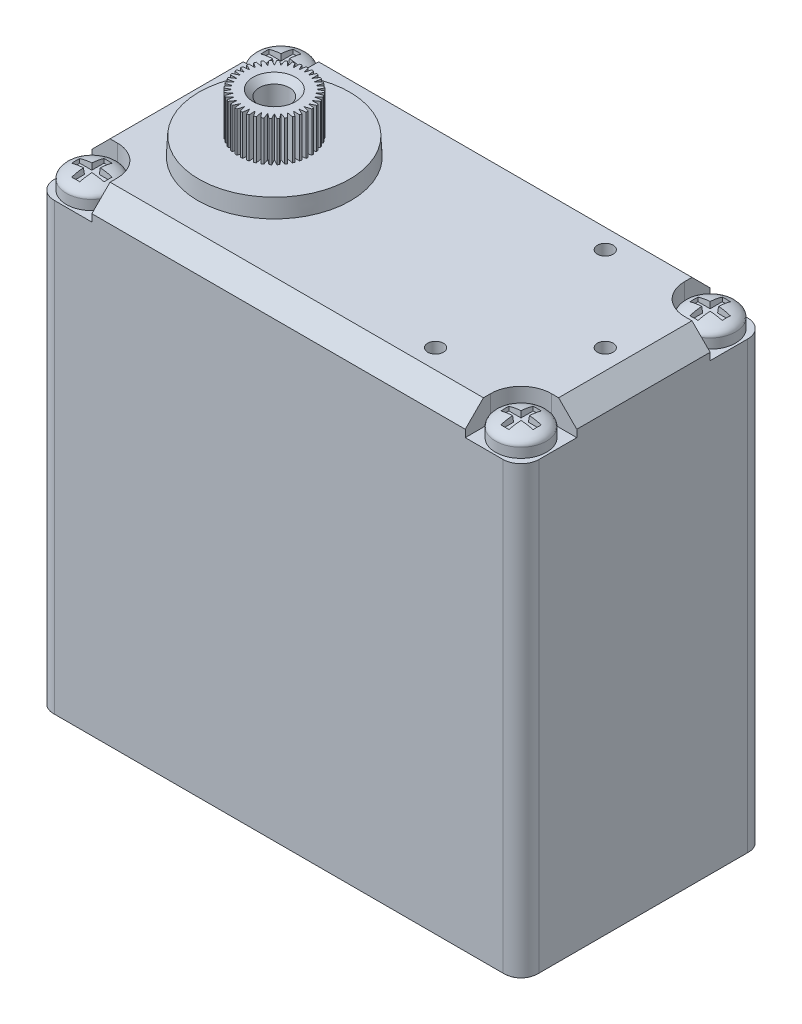
SolidWorks part; units mm, degrees
ref_plane "Front" through (0, 0, 0) normal (0, 0, 1) x (1, 0, 0)
ref_plane "Top" through (0, 0, 0) normal (0, 1, 0) x (1, 0, 0)
ref_plane "Right" through (0, 0, 0) normal (1, 0, 0) x (0, 0, -1)
sketch "Sketch1" plane through (0, 0, 0) normal (0, 0, 1) x (1, 0, 0)
  line L1 (20, 20.15) -> (-20, 20.15)
  line L2 (20, 20.15) -> (20, -20.15)
  line L3 (20, -20.15) -> (-20, -20.15)
  line L4 (-20, 20.15) -> (-20, -20.15)
  line L5 (20, 20.15) -> (-20, -20.15) construction
  line L6 (20, -20.15) -> (-20, 20.15) construction
  point P0 (0, 0)
  dimension "D1" = 40
  dimension "D2" = 40.3
extrude "Boss-Extrude1" add sketch "Sketch1" along normal mid plane 20.2
sketch "Sketch2" plane through (0, -20.15, 0) normal (0, -1, 0) x (1, 0, 0)
  line L1 (-20, 10.1) -> (-20, -10.1) construction
  circle A0 centre (-10.45, 0) radius 6.3
  dimension "D1" = 12.6
  dimension "D2" = 3.25
  dimension "D3" = 9.55
extrude "Boss-Extrude2" add sketch "Sketch2" along normal blind 1.5 draft 3
sketch "Sketch3" plane through (0, -20.15, 0) normal (0, -1, 0) x (1, 0, 0)
  circle A0 centre (-10.45, 0) radius 3
  dimension "D1" = 6
extrude "Boss-Extrude3" add sketch "Sketch3" along normal blind 5.4
sketch "Sketch9" plane through (0, -25.55, 0) normal (0, -1, 0) x (1, 0, 0)
  circle A0 centre (-10.45, 0) radius 1.2
  dimension "D1" = 2.4
extrude "Cut-Extrude4" cut sketch "Sketch9" against normal blind 5
sketch "Sketch4" plane through (0, 20.15, 0) normal (0, 1, 0) x (1, 0, 0)
  circle A1 centre (-10.45, 0) radius 6.3
  circle A2 centre (-10.45, 0) radius 6.3
  dimension "D1" = 0
extrude "Boss-Extrude4" add sketch "Sketch4" along normal blind 1.5 draft 3
sketch "Sketch5" plane through (0, 21.65, 0) normal (0, 1, 0) x (1, 0, 0)
  circle A0 centre (-10.45, 0) radius 2.95
  dimension "D1" = 5.9
extrude "Boss-Extrude5" add sketch "Sketch5" along normal blind 3.3 separate body
sketch "Sketch7" plane through (0, 24.95, 0) normal (0, 1, 0) x (1, 0, 0)
  circle A0 centre (-10.45, 0) radius 1.25
  dimension "D1" = 2.5
extrude "Cut-Extrude2" cut sketch "Sketch7" against normal blind 5
sketch "Sketch8" plane through (0, 24.95, 0) normal (0, 1, 0) x (1, 0, 0)
  line L0 (-8, 0) -> (-7.5, 0.15)
  line L1 (-8, 0) -> (-7.5, -0.15)
  line L2 (-7.5, -0.15) -> (-7.5, 0.15)
  circle A1 centre (-10.45, 0) radius 2.95 construction
  point P2 (-7.5, 0)
  dimension "D1" = 0.5
  dimension "D2" = 0.3
extrude "Cut-Extrude3" cut sketch "Sketch8" against normal through all
sketch "Sketch10" plane through (-20, 0, 0) normal (-1, 0, 0) x (0, 0, 1)
  line L0 (10.1, -20.15) -> (-10.1, -20.15) construction
  line L1 (3.5, -9.85) -> (-3.5, -9.85)
  line L2 (3.5, -9.85) -> (3.5, -13.35)
  line L3 (3.5, -13.35) -> (-3.5, -13.35)
  line L4 (-3.5, -9.85) -> (-3.5, -13.35)
  line L5 (3.5, -9.85) -> (-3.5, -13.35) construction
  line L6 (3.5, -13.35) -> (-3.5, -9.85) construction
  point P0 (0, -11.6)
  dimension "D1" = 7
  dimension "D2" = 3.5
  dimension "D3" = 6.8
extrude "Cut-Extrude5" cut sketch "Sketch10" against normal blind 4.9
sketch "Sketch11" plane through (-15.1, 0, 0) normal (-1, 0, 0) x (0, 0, 1)
  line L1 (-0.25, -12.55) -> (0.25, -12.55)
  line L2 (-0.25, -12.55) -> (-0.25, -12.05)
  line L3 (-0.25, -12.05) -> (0.25, -12.05)
  line L4 (0.25, -12.55) -> (0.25, -12.05)
  line L5 (-0.25, -12.55) -> (0.25, -12.05) construction
  line L6 (-0.25, -12.05) -> (0.25, -12.55) construction
  line L7 (3.5, -13.35) -> (-3.5, -13.35) construction
  line L9 (1.75, -12.55) -> (2.25, -12.55)
  line L10 (1.75, -12.55) -> (1.75, -12.05)
  line L11 (1.75, -12.05) -> (2.25, -12.05)
  line L12 (2.25, -12.55) -> (2.25, -12.05)
  line L13 (1.75, -12.55) -> (2.25, -12.05) construction
  line L14 (1.75, -12.05) -> (2.25, -12.55) construction
  line L15 (-2.25, -12.55) -> (-1.75, -12.55)
  line L16 (-2.25, -12.55) -> (-2.25, -12.05)
  line L17 (-2.25, -12.05) -> (-1.75, -12.05)
  line L18 (-1.75, -12.55) -> (-1.75, -12.05)
  line L19 (-2.25, -12.55) -> (-1.75, -12.05) construction
  line L20 (-2.25, -12.05) -> (-1.75, -12.55) construction
  point P0 (0, -12.3)
  point P5 (2, -12.3)
  point P13 (-2, -12.3)
  dimension "D1" = 0.5
  dimension "D2" = 0.8
  dimension "D3" = 1.5
  dimension "D4" = 1.5
extrude "Boss-Extrude6" add sketch "Sketch11" along normal blind 3.5 separate body
chamfer "Chamfer4" distance 0.1 angle 45 4 edges at (-18.6, -12.55, -2) (-18.6, -12.3, -2.25) (-18.6, -12.05, -2) (-18.6, -12.3, -1.75)
chamfer "Chamfer5" distance 0.1 angle 45 4 edges at (-18.6, -12.55, 0) (-18.6, -12.3, -0.25) (-18.6, -12.05, 0) (-18.6, -12.3, 0.25)
chamfer "Chamfer6" distance 0.1 angle 45 4 edges at (-18.6, -12.55, 2) (-18.6, -12.3, 1.75) (-18.6, -12.05, 2) (-18.6, -12.3, 2.25)
pattern_circular "CirPattern1" count 40 over 360 about axis through (-10.45, 24.95, 0) along (0, -1, 0) of "Cut-Extrude3" reverse direction yes
sketch "Sketch6" plane through (0, 20.15, 0) normal (0, 1, 0) x (1, 0, 0)
  line L0 (20, 10.1) -> (-20, 10.1) construction
  line L1 (-20, 10.1) -> (-15.4, 10.1)
  line L2 (-20, 10.1) -> (-20, 5.5)
  line L3 (-20, 5.5) -> (-17.9, 5.5)
  line L4 (-15.4, 10.1) -> (-15.4, 8)
  line L5 (-20, -10.1) -> (-20, 10.1) construction
  line L6 (0, -11.11) -> (0, 11.11) construction
  line L7 (15.4, 10.1) -> (15.4, 8)
  line L8 (20, 5.5) -> (17.9, 5.5)
  line L9 (20, 10.1) -> (20, 5.5)
  line L10 (20, 10.1) -> (15.4, 10.1)
  line L11 (-22, 0) -> (22, 0) construction
  line L12 (20, -10.1) -> (15.4, -10.1)
  line L13 (20, -10.1) -> (20, -5.5)
  line L14 (20, -5.5) -> (17.9, -5.5)
  line L15 (15.4, -10.1) -> (15.4, -8)
  line L16 (-15.4, -10.1) -> (-15.4, -8)
  line L17 (-20, -5.5) -> (-17.9, -5.5)
  line L18 (-20, -10.1) -> (-20, -5.5)
  line L19 (-20, -10.1) -> (-15.4, -10.1)
  arc A0 (-17.9, 5.5) -> (-15.4, 8) centre (-17.9, 8) ccw
  arc A1 (17.9, 5.5) -> (15.4, 8) centre (17.9, 8) cw
  arc A2 (17.9, -5.5) -> (15.4, -8) centre (17.9, -8) ccw
  arc A3 (-17.9, -5.5) -> (-15.4, -8) centre (-17.9, -8) cw
  dimension "D1" = 2.5
  dimension "D2" = 4.6
extrude "Cut-Extrude1" cut sketch "Sketch6" against normal blind 2.1
chamfer "Chamfer2" distance 1.5 angle 45 4 edges at (20, -20.15, 0) (0, -20.15, -10.1) (-20, -20.15, 0) (0, -20.15, 10.1)
fillet "Fillet1" radius 1.5 4 edges at (20, -0.3, -10.1) (20, -0.3, 10.1) (-20, -0.3, -10.1) (-20, -0.3, 10.1)
fillet "Fillet2" radius 2.1 4 edges at (-19.0303, -19.6197, 9.1303) (19.0303, -19.6197, 9.1303) (19.0303, -19.6197, -9.1303) (-19.0303, -19.6197, -9.1303)
chamfer "Chamfer1" distance 1.5 angle 45 4 edges at (20, 20.15, 0) (-20, 20.15, 0) (0, 20.15, -10.1) (0, 20.15, 10.1)
chamfer "Chamfer3" distance 0.5 angle 45 1 edges at (-11.7, 24.95, 0)
fillet "Fillet3" radius 0.5 1 edges at (-7.45, -25.55, 0)
sketch "Sketch12" plane through (0, 18.05, 0) normal (0, 1, 0) x (1, 0, 0)
  line L0 (-20, 10.1) -> (-15.4, 10.1) construction
  line L1 (-20, 10.1) -> (-20, 5.5) construction
  circle A0 centre (-17.7, 7.8) radius 2.1
  point P4 (-17.7, 10.1)
  point P7 (-20, 7.8)
  dimension "D1" = 4.2
extrude "Boss-Extrude7" add sketch "Sketch12" along normal blind 0.8 separate body
dome "Dome1" faces to dome 1 distance 0.8 reverse direction no elliptical dome yes face at (-19.8, 18.85, -7.8) parameters "D1"=0.8
sketch "Sketch13" plane through (0, 18.05, 0) normal (0, -1, 0) x (1, 0, 0)
  line L1 (-17.35, -6.45) -> (-18.05, -6.45)
  line L2 (-17.35, -6.45) -> (-17.35, -9.15)
  line L3 (-17.35, -9.15) -> (-18.05, -9.15)
  line L4 (-18.05, -6.45) -> (-18.05, -9.15)
  line L5 (-17.35, -6.45) -> (-18.05, -9.15) construction
  line L6 (-17.35, -9.15) -> (-18.05, -6.45) construction
  line L7 (-19.05, -8.15) -> (-16.35, -8.15)
  line L8 (-19.05, -8.15) -> (-19.05, -7.45)
  line L9 (-19.05, -7.45) -> (-16.35, -7.45)
  line L10 (-16.35, -8.15) -> (-16.35, -7.45)
  line L11 (-19.05, -8.15) -> (-16.35, -7.45) construction
  line L12 (-19.05, -7.45) -> (-16.35, -8.15) construction
  circle A0 centre (-17.7, -7.8) radius 2.1 construction
  point P0 (-17.7, -7.8)
  point P7 (-17.7, -7.8)
  dimension "D1" = 2.7
  dimension "D2" = 0.7
extrude "Cut-Extrude6" cut sketch "Sketch13" along normal blind 0.5 draft 5 from offset 1.6 contours L9 L8 L7 L4 | L4 L9 L2 L1 | L7 L10 L9 L2 | L7 L4 L3 L2 | L9 L4 L7 L2 region at (-17.7, 18.05, -6.95) region at (-16.85, 18.05, -7.8) region at (-17.7, 18.05, -7.8) region at (-18.55, 18.05, -7.8) region at (-17.7, 18.05, -8.65) offset against normal yes
mirror "Mirror1" about plane through (0, 0, 0) normal (1, 0, 0) of bodies 116
mirror "Mirror2" about plane through (0, 0, 0) normal (0, 0, 1) of bodies 117 116
sketch "Sketch14" plane through (0, -20.15, 0) normal (0, -1, 0) x (1, 0, 0)
  line L0 (22, 0) -> (-22, 0) construction
  line L1 (2.35, 7.5) -> (17.35, 7.5) construction
  line L2 (17.35, -7.5) -> (17.35, 7.5) construction
  line L5 (2.35, 7.5) -> (17.35, -7.5) construction
  circle A0 centre (17.35, 7.5) radius 0.65
  circle A1 centre (2.35, 7.5) radius 0.65
  circle A2 centre (2.35, -7.5) radius 0.65
  circle A3 centre (17.35, -7.5) radius 0.65
  point P4 (17.35, 0)
  point P11 (9.85, 0)
  dimension "D1" = 1.3
  dimension "D2" = 15
  dimension "D4" = 2.65
extrude "Cut-Extrude7" cut sketch "Sketch14" against normal blind 2
ref_axis "Axis1" through (9.85, -20.15, 0) along (0, -1, 0)
sketch "Sketch15" plane through (0, 20.15, 0) normal (0, 1, 0) x (1, 0, 0)
  circle A0 centre (9.85, 7) radius 0.65
  circle A1 centre (16.85, 0) radius 0.65
  circle A2 centre (9.85, -7) radius 0.65
  dimension "D1" = 1.3
extrude "Cut-Extrude8" cut sketch "Sketch15" against normal blind 2
